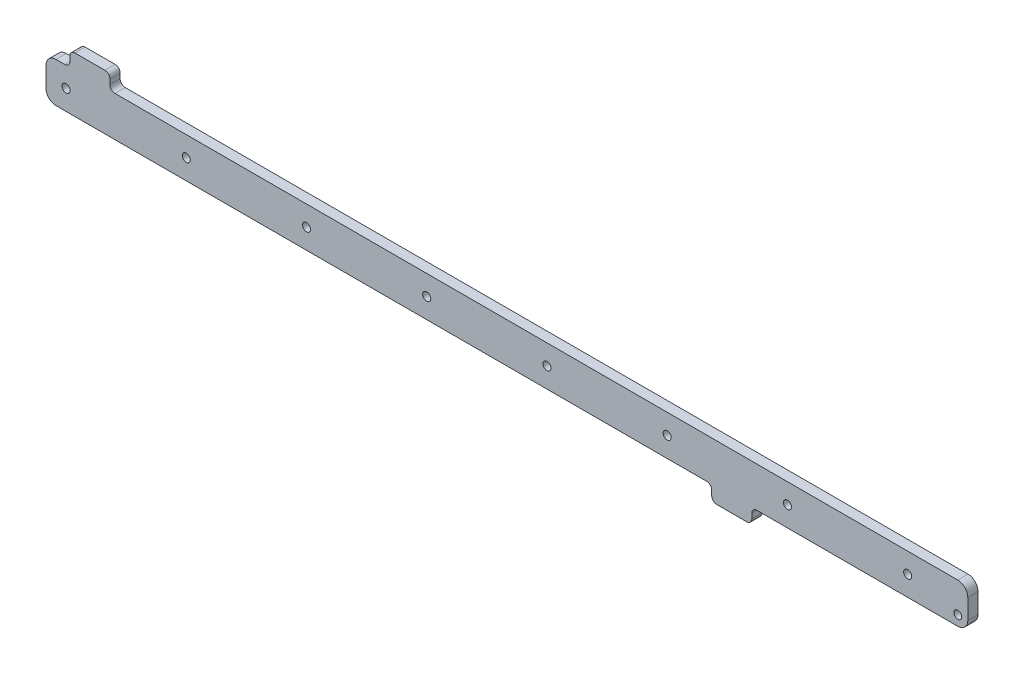
SolidWorks part; units mm, degrees
material "PC High Viscosity"
ref_plane "Front Plane" through (0, 0, 0) normal (0, 0, 1) x (1, 0, 0)
ref_plane "Top Plane" through (0, 0, 0) normal (0, 1, 0) x (1, 0, 0)
ref_plane "Right Plane" through (0, 0, 0) normal (1, 0, 0) x (0, 0, -1)
sketch "Sketch1" plane through (0, 0, 0) normal (0, 0, 1) x (1, 0, 0)
  line L1 (0, 0) -> (40.5308, 0)
  line L2 (0, 0) -> (0, 25.4)
  line L3 (0, 25.4) -> (15.1307, 25.4)
  line L4 (584.2, 0) -> (584.2, 25.4)
  line L5 (15.1307, 34.925) -> (40.5307, 34.925)
  line L6 (40.5307, 34.925) -> (40.5307, 25.4)
  line L7 (15.1307, 34.925) -> (15.1307, 25.4)
  line L11 (584.2, 10.0162) -> (577.85, 13.6823) construction
  line L12 (577.85, 13.6823) -> (571.5, 10.0162) construction
  line L13 (571.5, 10.0162) -> (571.5, 2.6838) construction
  line L14 (571.5, 2.6838) -> (577.85, -0.9823) construction
  line L15 (577.85, -0.9823) -> (584.2, 2.6838) construction
  line L16 (584.2, 2.6838) -> (584.2, 10.0162) construction
  line L19 (421.9033, 0) -> (421.9033, -9.525)
  line L20 (421.9033, -9.525) -> (447.3033, -9.525)
  line L21 (447.3033, -9.525) -> (447.3033, 0)
  line L22 (40.5307, 25.4) -> (584.2, 25.4)
  line L23 (40.5308, 0) -> (421.9033, 0)
  line L24 (447.3033, 0) -> (584.2, 0)
  circle A0 centre (577.85, 6.35) radius 2.4892
  circle A1 centre (577.85, 6.35) radius 6.35 construction
  dimension "D5" = 4.9784
  dimension "D6" = 9.525
  dimension "D7" = 12.7
  dimension "D1" = 584.2
  dimension "D2" = 25.4
  dimension "D3" = 25.4
  dimension "D4" = 421.9033
  dimension "D8" = 40.5307
  dimension "D9" = 25.4
extrude "Boss-Extrude1" add sketch "Sketch1" along normal blind 6.477 contours L6 L5 L3 | L1 L4 L3 L2 A0 | L1 region at (289.8115, 12.7081, 0)
fillet "Fillet2" radius 6.35 4 edges at (0, 0, 3.2385) (0, 25.4, 3.2385) (584.2, 25.4, 3.2385) (584.2, 0, 3.2385)
sketch "Sketch2" plane through (0, 0, 6.477) normal (0, 0, 1) x (1, 0, 0)
  line L0 (6.35, 25.4) -> (15.1307, 25.4) construction
  line L1 (584.2, 19.05) -> (584.2, 6.35) construction
  circle A0 centre (546.1, 12.7) radius 2.0193
  dimension "D1" = 4.0386
  dimension "D2" = 12.7
  dimension "D3" = 38.1
hole_wizard "CSK for #10 Flat Head Machine Screw (100)1" positions "Sketch4" profile "Sketch5" countersink size "#10" standard "ANSI Inch" end condition through all
sketch "Sketch4" plane through (0, 0, 6.477) normal (0, 0, 1) x (1, 0, 0)
  line L0 (584.2, 12.7) -> (0, 12.7) construction
  line L1 (584.2, 19.05) -> (584.2, 6.35) construction
  line L2 (0, 6.35) -> (0, 19.05) construction
  line L3 (6.35, 25.4) -> (15.1307, 25.4) construction
  point P11 (546.1, 12.7)
  dimension "D1" = 12.7
  dimension "D2" = 38.1
sketch "Sketch5" plane through (546.1, 12.7, 6.477) normal (1, 0, 0) x (0, -1, 0)
  line L0 (0, 0) -> (0, 6.477)
  line L1 (0, 6.477) -> (2.5527, 6.477)
  line L2 (2.5527, 6.477) -> (2.5527, 1.9608)
  line L3 (2.5527, 1.9608) -> (4.8895, 0)
  line L5 (4.8895, 0) -> (0, 0)
  line L6 (-2.5527, 1.9608) -> (-4.8895, 0) construction
  line L11 (0, -6.35) -> (0, 107.95) construction
  dimension "Thru Hole Dia." = 5.1054
  dimension "Thru Hole Depth" = 6.477
  dimension "Near C'Sink Dia." = 9.779
  dimension "Near C'Sink Angle" = 100
pattern_linear "LPattern1" count 8 spacing 76.2 along (-1, 0, 0) of "CSK for #10 Flat Head Machine Screw (100)1"
mirror "Mirror2" about plane through (0, 0, 0) normal (0, 0, 1) of bodies 108
delete or keep bodies "Body-Delete/Keep 1" type delete bodies bodies 108
fillet "Fillet3" radius 3.175 8 edges at (447.3033, 0, -3.2385) (447.3033, -9.525, -3.2385) (421.9033, -9.525, -3.2385) (421.9033, 0, -3.2385) (40.5307, 25.4, -3.2385) (40.5307, 34.925, -3.2385) (15.1307, 34.925, -3.2385) (15.1307, 25.4, -3.2385)
